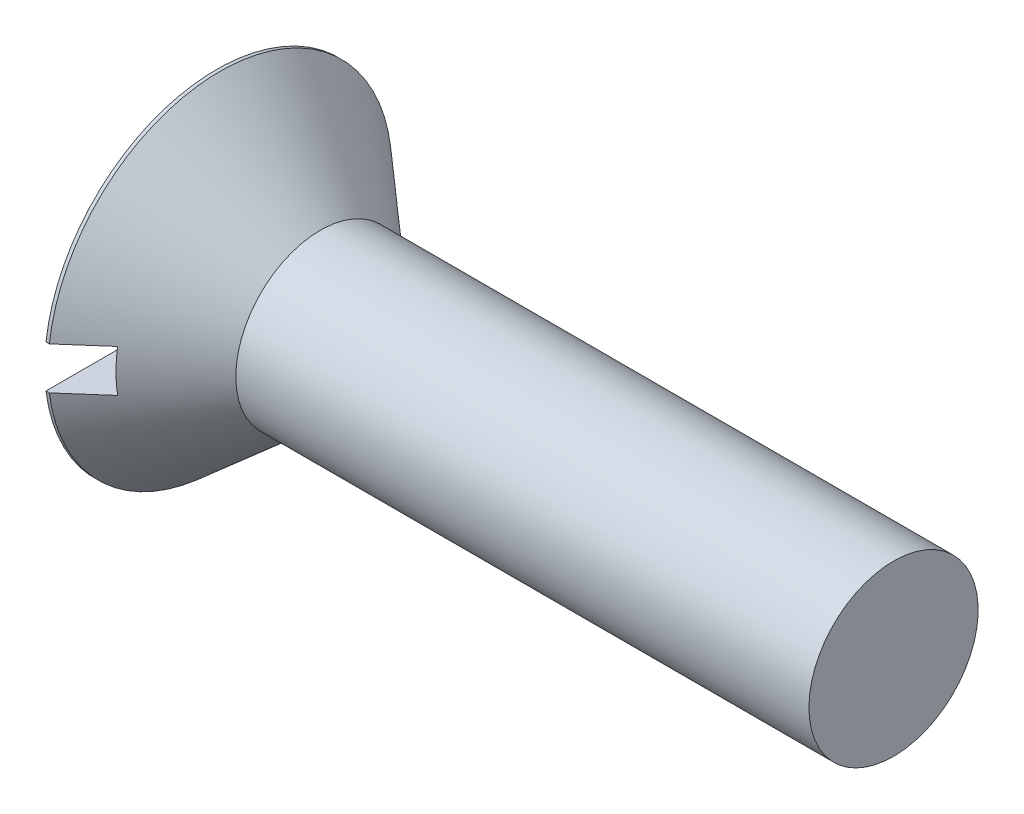
SolidWorks part; units mm, degrees
revolve "Base-Revolve" add sketch "BodySke" angle 360 about L5
sketch "BodySke" plane through (0, 0, 0) normal (0, 0, 1) x (1, 0, 0)
  line L0 (0, 0) -> (0, 9.6774)
  line L1 (0, 9.6774) -> (0.1881, 9.6774)
  line L2 (5.842, 4.7625) -> (38.1, 4.7625)
  line L3 (38.1, 4.7625) -> (38.1, 0)
  line L4 (38.1, 0) -> (0, 0)
  line L5 (-6.35, 0) -> (82.55, 0) construction
  line L6 (5.842, -4.7625) -> (38.1, -4.7625) construction
  line L7 (0.1881, -9.6774) -> (5.842, -4.7625) construction
  line L8 (0.1881, 9.6774) -> (5.842, 4.7625)
  line L9 (0, -9.6774) -> (0.1881, -9.6774) construction
  line L10 (7.4295, 6.35) -> (7.4295, -3.175) construction
  line L11 (6.35, 6.35) -> (6.35, -3.175) construction
  dimension "D6" = 0.1881
  dimension "Diameter" = 9.525
cosmetic thread "ThreadCosmetic" [suppressed] parameters "Thread_length"=30.6705, "Thread_minor"=7.9248
extrude "Slot" cut sketch "Sketch2" against normal blind 2.2352
sketch "Sketch2" plane through (0, 0, 0) normal (-1, 0, 0) x (0, 0, 1)
  line L0 (-9.6774, -1.1938) -> (9.6774, -1.1938)
  line L1 (-9.6774, -1.1938) -> (-9.6774, 1.1938)
  line L2 (9.6774, 1.1938) -> (-9.6774, 1.1938)
  line L3 (9.6774, 1.1938) -> (9.6774, -1.1938)
  dimension "D1" = 1.1938
  dimension "D2" = 19.3548
  dimension "D3" = 9.6774
ref_plane "Plane1" through (0, 0, 0) normal (0, 0, 1) x (1, 0, 0)
ref_plane "Plane2" through (0, 0, 0) normal (0, 1, 0) x (1, 0, 0)
ref_plane "Plane3" through (0, 0, 0) normal (1, 0, 0) x (0, 0, -1)
sketch "Sketch3" plane through (0, 0, 0) normal (-1, 0, 0) x (0, 0, 1)
  line L0 (-1.0922, 6.6421) -> (1.0922, 6.6421)
  line L1 (1.0922, 6.6421) -> (1.0922, -6.6421)
  line L2 (1.0922, -6.6421) -> (-1.0922, -6.6421)
  line L3 (-1.0922, -6.6421) -> (-1.0922, 6.6421)
  dimension "Cross_dia" = 13.2842
  dimension "Cross_width" = 2.1844
  dimension "D1" = 6.6421
  dimension "D2" = 1.0922
ref_plane "Plane4" through (7.9756, 0, 0) normal (-1, 0, 0) x (0, 0, 1)
sketch "Sketch4" plane through (7.9756, 0, 0) normal (-1, 0, 0) x (0, 0, 1)
  line L0 (-0.5461, 0.5461) -> (0.5461, 0.5461)
  line L3 (0.5461, 0.5461) -> (0.5461, -0.5461)
  line L4 (0.5461, -0.5461) -> (-0.5461, -0.5461)
  line L5 (-0.5461, -0.5461) -> (-0.5461, 0.5461)
  dimension "D2" = 1.0922
  dimension "D1" = 1.0922
  dimension "D3" = 0.5461
  dimension "D4" = 0.5461
loft "Cross" cut profiles "Sketch3", "Sketch4"
pattern_circular "CirPattern1" count 2 every 90 about axis through (-6.35, 0, 0) along (1, 0, 0) of "Cross"
sketch "ThdSchSke" plane through (0, 0, 0) normal (0, 0, 1) x (1, 0, 0)
  line L0 (7.4295, -3.9624) -> (6.8693, -4.7625)
  line L1 (7.4295, -3.9624) -> (7.9898, -4.7625)
  line L2 (7.9898, -4.7625) -> (7.9898, -5.9531)
  line L3 (-3.175, 0) -> (5.1513, 0) construction
  line L5 (7.9898, -5.9531) -> (6.8693, -5.9531)
  line L6 (6.8693, -5.9531) -> (6.8693, -4.7625)
  line L7 (0, 9.6774) -> (0, 1.1938) construction
  dimension "Thread_minor" = 7.9248
  dimension "Diameter" = 9.525
  dimension "Start" = 7.4295
revolve "ThreadSchematic" [suppressed] cut sketch "ThdSchSke" angle 360 about L3
pattern_linear "ThdSchPat" [suppressed]
equation "\"D1@Sketch3\" = \"Cross_dia@Sketch3\" / 2"
equation "\"D2@Sketch3\" = \"Cross_width@Sketch3\" / 2"
equation "\"D1@Sketch4\" = \"Cross_width@Sketch3\" *.5"
equation "\"D2@Sketch4\" = \"D1@Sketch4\""
equation "\"D4@Sketch4\" = \"D2@Sketch4\" / 2"
equation "\"D3@Sketch4\" = \"D1@Sketch4\" / 2"
equation "\"D1@Sketch2\" = \"Slot_width@Sketch2\" / 2"
equation "\"D2@Sketch2\" = \"Head_dia@BodySke\""
equation "\"D3@Sketch2\" = \"D2@Sketch2\" / 2"
equation "\"Thread_length@ThreadCosmetic\" = ((sgn( (\"Length@BodySke\" - \"Advance@BodySke\" - \"Head_ht@BodySke\" ) - \"Thread_nom@BodySke\" )-1)*( (\"Length@BodySke\" - \"Advance@BodySke\" - \"Head_ht@BodySke\" ) - \"Thread_nom@BodySke\" ))/-2+ \"Thread_nom@BodySke\""
equation "\"Thread_minor@ThdSchSke\" = \"Thread_minor@ThreadCosmetic\""
equation "\"Diameter@ThdSchSke\" = \"Diameter@BodySke\""
equation "\"Overcut@ThdSchSke\" = \"Diameter@BodySke\" * 1.25"
equation "\"Start@ThdSchSke\" = 0.000001 + \"Length@BodySke\" - \"Thread_length@ThreadCosmetic\"  '---Countersunk---"
equation "\"Num_threads@ThdSchPat\" = int( \"Thread_length@ThreadCosmetic\" / \"Advance@BodySke\" + 0.999 )  + 1"
equation "\"Advance@ThdSchPat\" = \"Thread_length@ThreadCosmetic\" /  (\"Num_threads@ThdSchPat\" - 1) 'relax it"
